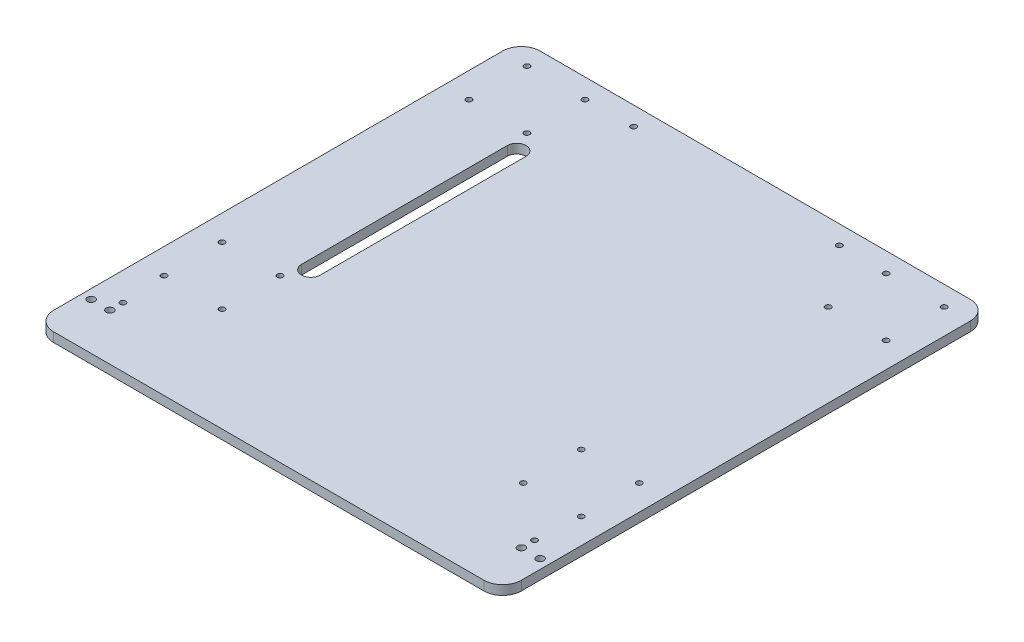
SolidWorks part; units mm, degrees
ref_plane "前视基准面" through (0, 0, 0) normal (0, 0, 1) x (1, 0, 0)
ref_plane "上视基准面" through (0, 0, 0) normal (0, 1, 0) x (1, 0, 0)
ref_plane "右视基准面" through (0, 0, 0) normal (1, 0, 0) x (0, 0, -1)
sketch "草图1" plane through (0, 0, 0) normal (0, 1, 0) x (1, 0, 0)
  line L0 (-125, 83) -> (-75, 83) construction
  line L1 (-125, -130) -> (125, -130)
  line L2 (-125, -130) -> (-125, 130)
  line L3 (-125, 130) -> (125, 130)
  line L4 (125, -130) -> (125, 130)
  line L5 (-125, -130) -> (125, 130) construction
  line L6 (-125, 130) -> (125, -130) construction
  line L7 (-125, -80) -> (-75, -80) construction
  line L8 (-125, -80) -> (-125, -38) construction
  line L9 (-125, -38) -> (-75, -38) construction
  line L10 (-75, -80) -> (-75, -38) construction
  line L11 (-117, -80) -> (-75, -80) construction
  line L12 (-117, -80) -> (-117, -38) construction
  line L13 (-117, -38) -> (-75, -38) construction
  line L14 (-75, -80) -> (-75, -38) construction
  line L15 (-117, -80) -> (-75, -38) construction
  line L16 (-117, -38) -> (-75, -80) construction
  line L17 (-111.5, -43.5) -> (-80.5, -43.5) construction
  line L18 (-111.5, -43.5) -> (-111.5, -74.5) construction
  line L19 (-111.5, -74.5) -> (-80.5, -74.5) construction
  line L20 (-80.5, -43.5) -> (-80.5, -74.5) construction
  line L21 (-125, 83) -> (-125, 125) construction
  line L22 (-125, 125) -> (-75, 125) construction
  line L23 (-75, 83) -> (-75, 125) construction
  line L24 (-117, 83) -> (-75, 83) construction
  line L25 (-117, 83) -> (-117, 125) construction
  line L26 (-117, 125) -> (-75, 125) construction
  line L27 (-75, 83) -> (-75, 125) construction
  line L28 (-117, 83) -> (-75, 125) construction
  line L29 (-117, 125) -> (-75, 83) construction
  line L30 (-111.5, 119.5) -> (-80.5, 119.5) construction
  line L31 (-111.5, 119.5) -> (-111.5, 88.5) construction
  line L32 (-111.5, 88.5) -> (-80.5, 88.5) construction
  line L33 (-80.5, 119.5) -> (-80.5, 88.5) construction
  line L34 (0, -130) -> (0, 130) construction
  line L35 (80.5, -43.5) -> (80.5, -74.5) construction
  line L36 (111.5, -74.5) -> (80.5, -74.5) construction
  line L37 (111.5, -43.5) -> (111.5, -74.5) construction
  line L38 (111.5, -43.5) -> (80.5, -43.5) construction
  line L39 (117, -38) -> (75, -80) construction
  line L40 (117, -80) -> (75, -38) construction
  line L41 (75, -80) -> (75, -38) construction
  line L42 (117, -38) -> (75, -38) construction
  line L43 (117, -80) -> (117, -38) construction
  line L44 (117, -80) -> (75, -80) construction
  line L45 (75, -80) -> (75, -38) construction
  line L46 (125, -38) -> (75, -38) construction
  line L47 (125, -80) -> (125, -38) construction
  line L48 (125, -80) -> (75, -80) construction
  line L49 (80.5, 119.5) -> (80.5, 88.5) construction
  line L50 (111.5, 88.5) -> (80.5, 88.5) construction
  line L51 (111.5, 119.5) -> (111.5, 88.5) construction
  line L52 (111.5, 119.5) -> (80.5, 119.5) construction
  line L53 (117, 125) -> (75, 83) construction
  line L54 (117, 83) -> (75, 125) construction
  line L55 (75, 83) -> (75, 125) construction
  line L56 (117, 125) -> (75, 125) construction
  line L57 (117, 83) -> (117, 125) construction
  line L58 (117, 83) -> (75, 83) construction
  line L59 (75, 83) -> (75, 125) construction
  line L60 (125, 125) -> (75, 125) construction
  line L61 (125, 83) -> (125, 125) construction
  line L62 (125, 83) -> (75, 83) construction
  line L63 (-75, 77.5) -> (-75, -32.5) construction
  line L64 (-70, 77.5) -> (-70, -32.5)
  line L65 (-80, 77.5) -> (-80, -32.5)
  circle A0 centre (-111.5, 119.5) radius 1.5
  circle A1 centre (-80.5, 119.5) radius 1.5
  circle A2 centre (-80.5, 88.5) radius 1.5
  circle A3 centre (-111.5, 88.5) radius 1.5
  circle A4 centre (-111.5, -43.5) radius 1.5
  circle A5 centre (-80.5, -43.5) radius 1.5
  circle A6 centre (-80.5, -74.5) radius 1.5
  circle A7 centre (-111.5, -74.5) radius 1.5
  circle A8 centre (111.5, -74.5) radius 1.5
  circle A9 centre (80.5, -74.5) radius 1.5
  circle A10 centre (80.5, -43.5) radius 1.5
  circle A11 centre (111.5, -43.5) radius 1.5
  circle A12 centre (111.5, 88.5) radius 1.5
  circle A13 centre (80.5, 88.5) radius 1.5
  circle A14 centre (80.5, 119.5) radius 1.5
  circle A15 centre (111.5, 119.5) radius 1.5
  circle A16 centre (-120, -105) radius 2
  circle A17 centre (-110, -105) radius 2
  circle A18 centre (110, -105) radius 2
  circle A19 centre (120, -105) radius 2
  circle A20 centre (-55, 120) radius 1.5
  circle A21 centre (55, 120) radius 1.5
  arc A22 (-70, 77.5) -> (-80, 77.5) centre (-75, 77.5) ccw
  circle A23 centre (-110, -98) radius 1.5
  arc A24 (-80, -32.5) -> (-70, -32.5) centre (-75, -32.5) ccw
  circle A25 centre (110, -98) radius 1.5
  point P0 (0, 0)
  point P10 (-96, -59)
  point P22 (-96, 104)
  point P38 (-96, 104)
  point P45 (-96, -59)
  point P58 (96, -59)
  point P73 (96, 104)
  point P89 (-75, 22.5)
  dimension "D14" = 3
  dimension "D15" = 3
  dimension "D9" = 10
  dimension "D17" = 4
  dimension "D18" = 4
  dimension "D22" = 10
  dimension "D23" = 3
  dimension "D21" = 55
  dimension "D24" = 3
  dimension "D25" = 15
  dimension "D26" = 18
  dimension "D28" = 5
  dimension "D1" = 250
  dimension "D2" = 260
  dimension "D3" = 50
  dimension "D4" = 5
  dimension "D5" = 42
  dimension "D6" = 31
  dimension "D7" = 50
  dimension "D8" = 42
  dimension "D10" = 31
  dimension "D11" = 50
  dimension "D12" = 5
  dimension "D19" = 25
  dimension "D20" = 25
  dimension "D27" = 50
  dimension "D29" = 110
  dimension "D30" = 52.5
  dimension "D13" = 4
  dimension "D16" = 4
extrude "凸台-拉伸1" add sketch "草图1" along normal blind 5
fillet "圆角2" radius 10 4 edges at (125, 2.5, -130) (125, 2.5, 130) (-125, 2.5, -130) (-125, 2.5, 130)
